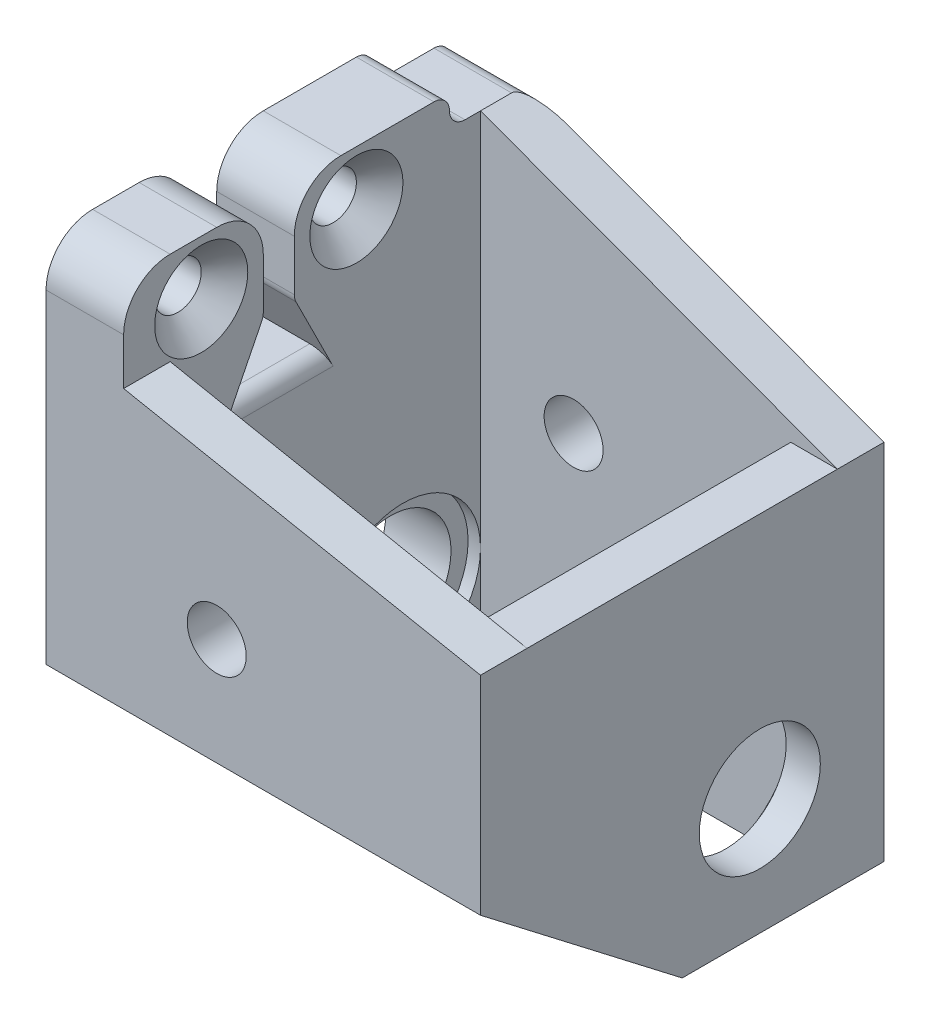
SolidWorks part; units mm, degrees
other "标注1"
sketch "草图49" plane through (13, 10.3992, -3) normal (0.763, 0.5413, -0.3534) x (-0.4894, 0.1265, -0.8629)
material "ABS"
ref_plane "前视基准面" through (0, 0, 0) normal (0, 0, 1) x (1, 0, 0)
ref_plane "上视基准面" through (0, 0, 0) normal (0, 1, 0) x (1, 0, 0)
ref_plane "右视基准面" through (0, 0, 0) normal (1, 0, 0) x (0, 0, -1)
sketch "草图1" plane through (0, 0, 0) normal (0, 0, 1) x (1, 0, 0)
  line L0 (10, 0) -> (-10, 0)
  line L1 (0, 4.2473) -> (0, -34.6143) construction
  line L2 (-10, 0) -> (-10, -57.766)
  line L3 (-10, -57.766) -> (10, -57.766)
  line L4 (10, 0) -> (10, -57.766)
  point P8 (0, -57.766)
  point P9 (0, 0)
extrude "凸台-拉伸1" add sketch "草图1" against normal blind 3
sketch "草图2" plane through (-10, 0, 0) normal (-1, 0, 0) x (0, 0, 1)
  line L1 (-3, 0) -> (23, 0)
  line L2 (-3, 0) -> (-3, -57.766)
  line L3 (-3, -57.766) -> (23, -57.766)
  line L4 (23, 0) -> (23, -57.766)
extrude "凸台-拉伸2" add sketch "草图2" along normal blind 3
sketch "草图3" plane through (0, 0, 0) normal (0, 0, 1) x (1, 0, 0)
  line L0 (-10, -5.5) -> (10, -5.5)
  line L1 (-10, -57.766) -> (-10, 0) construction
  line L2 (10, -57.766) -> (10, 0) construction
  line L3 (10, 0) -> (-10, 0) construction
  dimension "D1" = 5.5
sketch "草图4" plane through (-10, 0, 0) normal (1, 0, 0) x (0, 0, -1)
  line L0 (-23, -5.5) -> (0, -5.5)
  line L1 (-23, -57.766) -> (-23, 0) construction
  line L2 (0, 0) -> (0, -57.766) construction
  line L3 (-23, 0) -> (0, 0) construction
  dimension "D1" = 5.5
sketch "草图7" plane through (-10, 0, 0) normal (1, 0, 0) x (0, 0, -1)
  line L0 (-23, -14.9) -> (0, -14.9)
  line L1 (-23, -57.766) -> (-23, 0) construction
  line L2 (0, -57.766) -> (0, 0) construction
  line L3 (-23, -5.5) -> (0, -5.5) construction
  circle A0 centre (-5, -14.9) radius 3.9
  point P8 (-5, -14.9)
  dimension "D1" = 9.4
  dimension "D2" = 5
extrude "切除-拉伸1" cut sketch "草图7" against normal blind 6 contours L0 A0 | L0 A0 region at (-10, -13.2448, 5) region at (-10, -16.5552, 5)
sketch "草图8" plane through (-13, 0, 0) normal (-1, 0, 0) x (0, 0, 1)
  circle A0 centre (5, -14.9) radius 4.48
extrude "切除-拉伸2" cut sketch "草图8" against normal blind 0.8
sketch "草图9" plane through (0, 0, 0) normal (0, 0, 1) x (1, 0, 0)
  line L0 (-10, -5.5) -> (10, -5.5) construction
  circle A0 centre (-4, -5.5) radius 1.9
  point P0 (-4, -5.5)
  point P1 (-10, -5.5)
  point P4 (-4, -5.5)
  dimension "D1" = 6
extrude "切除-拉伸3" cut sketch "草图9" against normal blind 3.8
sketch "草图10" plane through (0, 0, 0) normal (0, 0, 1) x (1, 0, 0)
  line L0 (0, 1.0359) -> (0, 0) construction
  line L1 (0, 0) -> (0, -59.324) construction
ref_plane "基准面1" through (0, 0, 0) normal (1, 0, 0) x (0, 0, -1)
mirror "镜向1" about plane through (0, 0, 0) normal (1, 0, 0) of "凸台-拉伸2"
mirror "镜向2" about plane through (0, 0, 0) normal (1, 0, 0) of "切除-拉伸1", "切除-拉伸2"
ref_plane "基准面2" through (0, 0, 10) normal (0, 0, 1) x (1, 0, 0)
mirror "镜向3" about plane through (0, 0, 10) normal (0, 0, 1) of "凸台-拉伸1"
mirror "镜向5" about plane through (0, 0, 10) normal (0, 0, 1) of "切除-拉伸3"
sketch "草图12" plane through (13, 0, 0) normal (1, 0, 0) x (0, 0, -1)
  line L0 (-23, -22.4) -> (3, -22.4)
  line L1 (-23, -57.766) -> (-23, 0) construction
  line L2 (3, 0) -> (3, -57.766) construction
  line L5 (-23, -22.4) -> (-23, -57.766)
  line L6 (-23, -57.766) -> (3, -57.766)
  line L7 (3, -22.4) -> (3, -57.766)
  circle A0 centre (-5, -14.9) radius 3.9 construction
  dimension "D1" = 7.5
extrude "切除-拉伸4" cut sketch "草图12" against normal blind 36
sketch "草图22" plane through (13, 0, 0) normal (1, 0, 0) x (0, 0, -1)
  line L0 (-23, -12.4) -> (-23, -22.4)
  line L1 (-23, -22.4) -> (-23, 0) construction
  line L2 (-23, -22.4) -> (-10, -22.4)
  line L3 (3, -22.4) -> (-23, -22.4) construction
  line L4 (-23, -12.4) -> (-10, -22.4)
extrude "切除-拉伸8" cut sketch "草图22" against normal blind 28
sketch "草图23" plane through (0, 0, 0) normal (0, 1, 0) x (1, 0, 0)
  line L1 (-10, 0) -> (10, 0)
  line L2 (-10, 0) -> (-10, -20)
  line L3 (-10, -20) -> (10, -20)
  line L4 (10, 0) -> (10, -20)
  line L5 (13, -23) -> (-13, -23)
  line L6 (13, -23) -> (13, 3)
  line L7 (13, 3) -> (-13, 3)
  line L8 (-13, -23) -> (-13, 3)
extrude "凸台-拉伸7" add sketch "草图23" along normal blind 4
sketch "草图24" plane through (0, 4, 0) normal (0, 1, 0) x (1, 0, 0)
  line L0 (10, -20) -> (10, 0) construction
  line L1 (-10, 0) -> (10, 0)
  line L2 (-10, 0) -> (-10, -20)
  line L3 (-10, -20) -> (10, -20)
  line L4 (10, 0) -> (10, -20)
extrude "凸台-拉伸8" add sketch "草图24" against normal blind 3
sketch "草图25" plane through (0, 4, 0) normal (0, 1, 0) x (1, 0, 0)
  line L0 (13, -23) -> (13, 3) construction
  line L4 (13, -23) -> (18, -23)
  line L5 (13, -23) -> (13, -7)
  line L6 (13, -7) -> (18, -7)
  line L7 (18, -23) -> (18, -7)
  circle A0 centre (15.5, -20.2333) radius 1.5
  circle A1 centre (15.5, -10.2333) radius 1.5
  point P0 (13, -15)
  dimension "D1" = 8
extrude "凸台-拉伸9" add sketch "草图25" against normal blind 3 contours A1 | A0 | L5 L4 L7 L6 region at (15.5, 4, 20.2333) region at (15.5, 4, 10.2333)
fillet "圆角1" radius 1 1 edges at (18, 1, 15)
sketch "草图26" plane through (13, 0, 0) normal (1, 0, 0) x (0, 0, -1)
  line L0 (-23, 1) -> (-7, 1) construction
  line L1 (-16, 1) -> (-14, 1)
  arc A0 (-16, 1) -> (-14, 1) centre (-15, 1) ccw
extrude "切除-拉伸9" cut sketch "草图26" against normal blind 3
sketch "草图27" plane through (0, 4, 0) normal (0, 1, 0) x (1, 0, 0)
  circle A0 centre (7.5, -15.2333) radius 1.5
extrude "切除-拉伸10" cut sketch "草图27" against normal blind 3
sketch "草图28" plane through (0, 1, 0) normal (0, -1, 0) x (1, 0, 0)
  line L1 (-10, 20) -> (10, 20)
  line L2 (-10, 20) -> (-10, 0)
  line L3 (-10, 0) -> (10, 0)
  line L4 (10, 20) -> (10, 0)
extrude "切除-拉伸11" cut sketch "草图28" against normal blind 10
sketch "草图29" plane through (0, 0, -3) normal (0, 0, -1) x (-1, 0, 0)
  line L1 (13, 4) -> (-24.6816, 4)
  line L2 (13, 4) -> (13, 1)
  line L3 (13, 1) -> (-24.6816, 1)
  line L4 (-24.6816, 4) -> (-24.6816, 1)
extrude "切除-拉伸12" cut sketch "草图29" against normal blind 42
sketch "草图31" plane through (-12.2, 0, 0) normal (-1, 0, 0) x (0, 0, 1)
  circle A0 centre (5, -14.9) radius 3.98
  circle A1 centre (5, -14.9) radius 4.48
extrude "凸台-拉伸13" add sketch "草图31" along normal blind 0.8
sketch "草图32" plane through (-10, 0, 0) normal (1, 0, 0) x (0, 0, -1)
  circle A0 centre (-5, -14.9) radius 3.98
  circle A1 centre (-5, -14.9) radius 5
extrude "切除-拉伸13" cut sketch "草图32" against normal blind 0.8
sketch "草图33" plane through (13, 0, 0) normal (1, 0, 0) x (0, 0, -1)
  circle A0 centre (-5, -14.9) radius 4.48
extrude "凸台-拉伸14" add sketch "草图33" against normal blind 3
mirror "镜向6" about plane through (0, 0, 0) normal (1, 0, 0) of "切除-拉伸1", "切除-拉伸13"
sketch "草图36" plane through (-10.8, 0, 0) normal (1, 0, 0) x (0, 0, -1)
  circle A0 centre (-5, -14.9) radius 5
extrude "切除-拉伸14" cut sketch "草图36" along normal blind 3
mirror "镜向7" about plane through (0, 0, 0) normal (1, 0, 0) of "切除-拉伸14"
sketch "草图37" plane through (-12.2, 0, 0) normal (-1, 0, 0) x (0, 0, 1)
  circle A0 centre (5, -14.9) radius 3.9
  circle A1 centre (5, -14.9) radius 3.98
extrude "凸台-拉伸17" add sketch "草图37" along normal up to surface (0.8 mm away) up to face at (-13, -11.04, 10)
sketch "草图38" plane through (-13, 0, 0) normal (-1, 0, 0) x (0, 0, 1)
  line L0 (13, 1) -> (13, 8)
  line L1 (23, 1) -> (-3, 1) construction
  line L3 (11, 10.3992) -> (5, 10.3992)
  line L4 (15, 1) -> (21, 1)
  line L5 (15, 1) -> (15, 10.3992)
  line L6 (15, 10.3992) -> (21, 10.3992)
  line L7 (21, 1) -> (21, 10.3992)
  line L8 (5, 1) -> (5, 10.3992)
  line L9 (11, 1) -> (5, 1)
  line L10 (11, 1) -> (11, 10.3992)
  circle A0 centre (18, 8) radius 1.5
  circle A2 centre (8, 8) radius 1.5
  point P13 (15, 1)
  line M9 (23, 1) -> (-3, 1)
  dimension "D1" = 2
  dimension "D2" = 3
  dimension "D3" = 6
extrude "凸台-拉伸18" add sketch "草图38" against normal blind 3 contours L7 L6 L5 A0 M9 | L10 L3 L8 A2 M9 region at (-13, 5.37, 8) region at (-13, 5.37, 18)
sketch "草图39" plane through (13, 0, 0) normal (1, 0, 0) x (0, 0, -1)
  line L0 (-23, 1) -> (-16, 1) construction
  line L1 (-17.3818, 1) -> (-13.1942, 1)
  line L2 (-17.3818, 1) -> (-17.3818, -0.3609)
  line L3 (-17.3818, -0.3609) -> (-13.1942, -0.3609)
  line L4 (-13.1942, 1) -> (-13.1942, -0.3609)
extrude "凸台-拉伸19" add sketch "草图39" against normal blind 3
sketch "草图43" plane through (-13, 0, 0) normal (-1, 0, 0) x (0, 0, 1)
  line L0 (-3, 1) -> (5, 1)
  line L1 (5, 1) -> (5, 10.3992)
  line L2 (5, 10.3992) -> (11, 10.3992)
  line L3 (11, 10.3992) -> (11, 1)
  line L4 (11, 1) -> (15, 1)
  line L5 (15, 1) -> (15, 10.3992)
  line L6 (15, 10.3992) -> (21, 10.3992)
  line L7 (21, 10.3992) -> (21, 1)
  line L8 (21, 1) -> (23, 1)
  line L9 (23, 1) -> (23, -12.4)
  line L10 (23, -12.4) -> (10, -22.4)
  line L11 (10, -22.4) -> (-3, -22.4)
  line L12 (-3, -22.4) -> (-3, 1)
  circle A0 centre (8, 8) radius 1.5
  circle A1 centre (18, 8) radius 1.5
  circle A2 centre (5, -14.9) radius 3.9
extrude "凸台-拉伸22" add sketch "草图43" along normal blind 2
sketch "草图44" plane through (0, 0, 21) normal (0, 0, 1) x (1, 0, 0)
  line L1 (-15, 10.3992) -> (-10, 10.3992)
  line L2 (-15, 10.3992) -> (-15, 1)
  line L3 (-15, 1) -> (-10, 1)
  line L4 (-10, 10.3992) -> (-10, 1)
extrude "凸台-拉伸23" add sketch "草图44" along normal up to surface (2 mm away) up to face at (-4, -3.6, 23)
sketch "草图45" plane through (0, 0, 23) normal (0, 0, 1) x (1, 0, 0)
  line L1 (-10, 1) -> (13, 1)
  line L3 (-10, 1) -> (-10, 5.5)
  line L7 (-10, 10.3992) -> (-10, 1) construction
  line L8 (-10, 5.5) -> (13, 1)
extrude "凸台-拉伸24" add sketch "草图45" against normal up to surface (3 mm away) up to face at (0, -6.8538, 20)
sketch "草图47" plane through (0, 0, 5) normal (0, 0, -1) x (-1, 0, 0)
  line L6 (10, 1) -> (15, 1)
  line L7 (10, 1) -> (10, 10.3992)
  line L8 (10, 10.3992) -> (15, 10.3992)
  line L9 (15, 1) -> (15, 10.3992)
extrude "凸台-拉伸25" add sketch "草图47" along normal up to surface (8 mm away) up to face at (-2.1, -5.5, -3)
sketch "草图51" plane through (0, 10.3992, 0) normal (0, 1, 0) x (1, 0, 0)
  line L1 (-15, 3) -> (-10, 3)
  line L2 (-15, 3) -> (-15, -11)
  line L3 (-15, -11) -> (-10, -11)
  line L4 (-10, 3) -> (-10, -11)
  line L5 (-15, -15) -> (-10, -15)
  line L6 (-15, -15) -> (-15, -23)
  line L7 (-15, -23) -> (-10, -23)
  line L8 (-10, -15) -> (-10, -23)
extrude "凸台-拉伸28" add sketch "草图51" along normal blind 1.1
sketch "草图53" plane through (-10, 0, 0) normal (1, 0, 0) x (0, 0, -1)
  line L1 (3, 11.4992) -> (-2, 11.4992)
  line L2 (3, 11.4992) -> (3, 9.4992)
  line L3 (3, 9.4992) -> (-2, 9.4992)
  line L4 (-2, 11.4992) -> (-2, 9.4992)
extrude "切除-拉伸16" cut sketch "草图53" against normal blind 6.1
fillet "圆角9" radius 1 2 edges at (-12.5, 9.4992, 2) (-12.5, 11.4992, 2)
sketch "草图54" plane through (0, 0, -3) normal (0, 0, -1) x (-1, 0, 0)
  line L0 (-13, 1) -> (10, 1)
  line L1 (10, 1) -> (10, 9.4992)
  line L2 (10, 9.4992) -> (-13, 1)
extrude "凸台-拉伸30" add sketch "草图54" against normal up to surface (3 mm away) up to face at (0, -12.1, 0)
fillet "圆角10" radius 1 1 edges at (-12.5, 9.4992, -3)
sketch "草图56" plane through (-10, 0, 0) normal (1, 0, 0) x (0, 0, -1)
  circle A0 centre (-18, 8) radius 3
  circle A1 centre (-8, 8) radius 3
sketch "草图57" plane through (0, 0, 15) normal (0, 0, -1) x (-1, 0, 0)
  line L6 (15, 1) -> (10, 1)
  line L7 (15, 1) -> (15, 11.4992)
  line L8 (15, 11.4992) -> (10, 11.4992)
  line L9 (10, 1) -> (10, 11.4992)
extrude "凸台-拉伸31" add sketch "草图57" along normal blind 1
sketch "草图58" plane through (0, 0, 11) normal (0, 0, 1) x (1, 0, 0)
  line L1 (-15, 11.4992) -> (-10, 11.4992)
  line L2 (-15, 11.4992) -> (-15, 1)
  line L3 (-15, 1) -> (-10, 1)
  line L4 (-10, 11.4992) -> (-10, 1)
extrude "凸台-拉伸32" add sketch "草图58" along normal blind 1
sketch "草图59" plane through (-10, 0, 0) normal (1, 0, 0) x (0, 0, -1)
  circle A0 centre (-18, 8) radius 3.1
  circle A1 centre (-8, 8) radius 3.1
fillet "圆角11" radius 3 3 edges at (-12.5, 11.4992, 12) (-12.5, 11.4992, 14) (-12.5, 11.4992, 23)
sketch "草图61" plane through (-10, 0, 0) normal (1, 0, 0) x (0, 0, -1)
  line L0 (-12, 1) -> (-12, 5)
  line L1 (-12, 1) -> (-12, 8.4992) construction
  line L2 (-12, 5) -> (-10, 1)
  line L3 (-10, 1) -> (-12, 1)
  line L4 (-14, 1) -> (-14, 5)
  line L5 (-14, 8.4992) -> (-14, 1) construction
  line L6 (-14, 5) -> (-16, 1)
  line L7 (-16, 1) -> (-14, 1)
extrude "切除-拉伸19" cut sketch "草图61" against normal blind 6.5
fillet "圆角14" radius 1 1 edges at (-10, 1, 13)
fillet "圆角19" radius 1 2 edges at (-12.5, 5, 12) (-12.5, 5, 14)
hole_wizard "打孔尺寸(%根据)内六角花形沉头螺钉的类型1" positions "3D草图1" profile "草图62" countersink size "M6" standard "GB" end condition up to next
sketch3d "3D草图1"
  line L0 (-10, 8, 18) -> (-15, 8, 18) construction
  line L1 (-10, 8, 8) -> (-15, 8, 8) construction
  point P0 (-10, 8, 18)
  point P4 (-10, 8, 8)
sketch "草图62" plane through (-10, 8, 18) normal (0, 1, 0) x (0, 0, -1)
  line L0 (0, 0) -> (0, 5)
  line L1 (0, 5) -> (1.5, 5)
  line L2 (1.5, 5) -> (1.5, 1.5)
  line L3 (1.5, 1.5) -> (3, 0)
  line L5 (3, 0) -> (0, 0)
  line L6 (-1.5, 1.5) -> (-3, 0) construction
  line L11 (0, -6.35) -> (0, 107.95) construction
  dimension "通孔孔直径" = 3
  dimension "通孔孔深度" = 5
  dimension "近端锥形沉头孔直径" = 6
  dimension "近端锥形沉头孔角度" = 90
